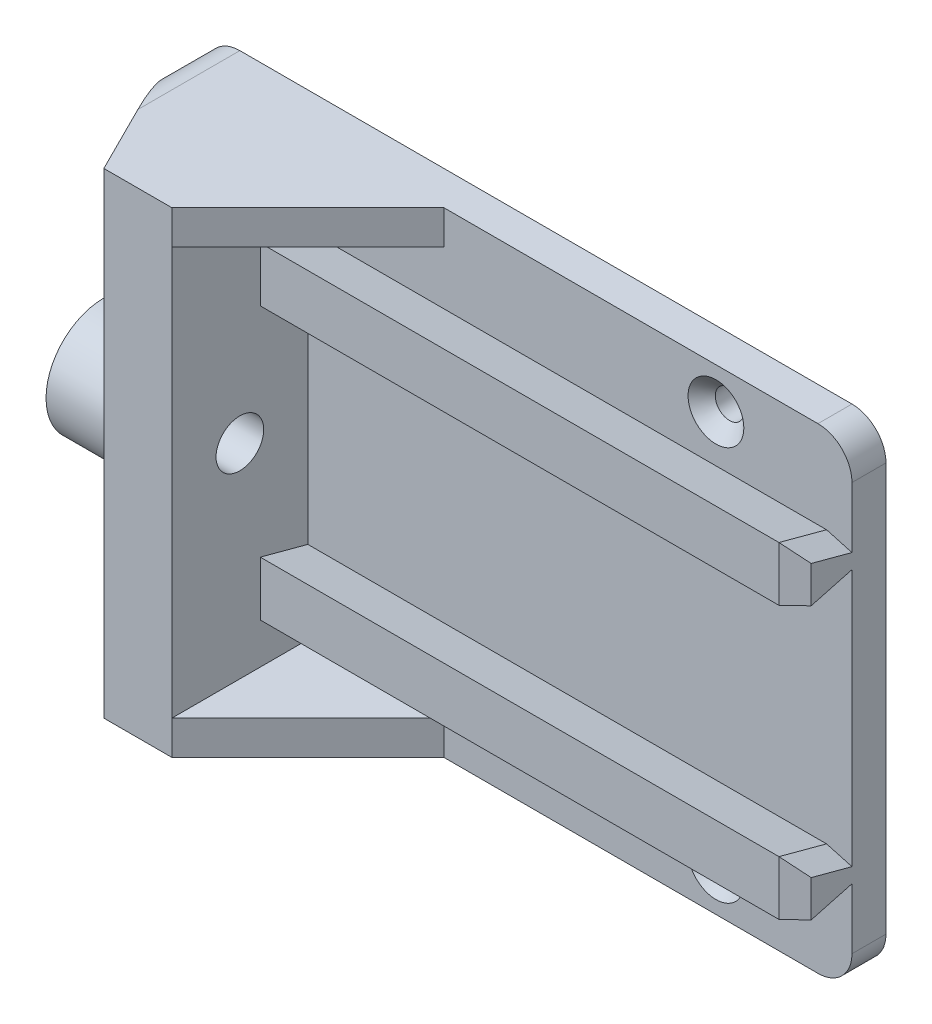
SolidWorks part; units mm, degrees
ref_plane "Piano frontale" through (0, 0, 0) normal (1, 0, 0) x (0, 1, 0)
ref_plane "Piano superiore - Base" through (0, 0, 0) normal (0, 0, 1) x (0, 1, 0)
ref_plane "Piano destro" through (0, 0, 0) normal (0, 1, 0) x (-1, 0, 0)
ref_plane "Alzata" through (0, 0, 30) normal (0, 0, 1) x (0, 1, 0)
ref_plane "Base scorrimento" through (0, 0, 5) normal (0, 0, 1) x (0, 1, 0)
sketch "Schizzo2" plane through (0, 0, 0) normal (0, 1, 0) x (-1, 0, 0)
  line L9 (-100, 0) -> (-100, 5)
  line L10 (38.5, 0) -> (-38.5, 0) construction
  line L11 (38.5, 5) -> (-38.5, 5) construction
  line L12 (-100, 5) -> (-20, 5)
  line L13 (-20, 5) -> (-20, 25)
  line L15 (-20, 25) -> (-10, 25)
  line L16 (-10, 25) -> (-10, 5)
  line L17 (-10, 5) -> (0, 5)
  line L18 (0, 5) -> (0, 0)
  line L19 (0, 0) -> (-100, 0)
  dimension "D1" = 10
  dimension "D2" = 80
  dimension "D3" = 10
  dimension "D4" = 20
extrude "Estrusione-Estrusione2" add sketch "Schizzo2" along normal mid plane 70
sketch "Schizzo8" plane through (20, 0, 0) normal (1, 0, 0) x (0, 1, 0)
  line L0 (-22.1244, 5) -> (-24, 12)
  line L1 (-24, 12) -> (-16, 12)
  line L2 (-16, 12) -> (-17.8756, 5)
  line L3 (-17.8756, 5) -> (-22.1244, 5)
  line L4 (35, 5) -> (-35, 5) construction
  line L5 (35, 5) -> (-35, 5) construction
  line L6 (0, -55) -> (0, 55) construction
  point P4 (-20, 5)
  dimension "D1" = 8
  dimension "D2" = 7
  dimension "D3" = 75
  dimension "D4" = 20
extrude "Estrusione-Estrusione4" add sketch "Schizzo8" along normal up to surface (80 mm away) up to face at (100, 0, 2.5)
sketch "Schizzo9" plane through (0, -35, 0) normal (0, -1, 0) x (1, 0, 0)
  line L0 (20, 25) -> (40, 5)
  line L1 (55, 5) -> (-55, 5) construction
  dimension "D1" = 45
rib "Nervatura2" sketch "Schizzo9" sketch "Schizzo9" thickness 5 extrusion direction parallel to sketch draft on no parameters "D1"=5
sketch "Schizzo10" plane through (0, -35, 0) normal (0, -1, 0) x (1, 0, 0)
  line L0 (10, 25) -> (0, 5)
rib "Nervatura3" sketch "Schizzo10" sketch "Schizzo10" thickness 5 extrusion direction parallel to sketch draft on no parameters "D1"=5
chamfer "Smusso2" distance 1 angle 75 3 edges at (100, -16.9378, 8.5) (100, -20, 12) (100, -23.0622, 8.5) first distance on face at (100, -10, 5.5)
mirror "Specchia3" about plane through (0, 0, 0) normal (0, 1, 0) of "Smusso2", "Estrusione-Estrusione4", "Nervatura2", "Nervatura3"
fillet "Raccordo2" radius 5 4 edges at (100, -35, 2.5) (0, -35, 2.5) (0, 35, 2.5) (100, 35, 2.5)
hole_wizard "Foro per Vite M6-1" positions "Schizzo11" profile "Schizzo12" hole size "M6" standard "Ansi Metric" end condition through all
sketch "Schizzo11" plane through (10, 0, 0) normal (-1, 0, 0) x (0, 0, 1)
  line L0 (55, 0) -> (-55, 0) construction
  line L1 (5, -55) -> (5, 55) construction
  point P1 (15, 0)
  dimension "D1" = 10
sketch "Schizzo12" plane through (10, 0, 15) normal (0, 1, 0) x (0, 0, 1)
  line L0 (0, 0) -> (0, 90)
  line L1 (0, 90) -> (3.5, 90)
  line L2 (3.5, 90) -> (3.5, 0)
  line L5 (3.5, 0) -> (0, 0)
  line L11 (0, -6.35) -> (0, 107.95) construction
  dimension "Thru Hole Dia." = 7
  dimension "Thru Hole Depth" = 90
hole_wizard "Foro svasato per Vite M3.5-1" positions "Schizzo13" profile "Schizzo14" countersink size "M3.5" standard "Ansi Metric" end condition through all
sketch "Schizzo13" plane through (0, 0, 5) normal (0, 0, 1) x (1, 0, 0)
  line L6 (40, -35) -> (95, -35) construction
  line L8 (95, -35) -> (5, -35) construction
  line L9 (0, 30) -> (0, -30) construction
  line L10 (100, -21.0891) -> (100, -30) construction
  point P0 (5, -20)
  point P2 (80, -29)
  dimension "D1" = 15
  dimension "D2" = 20
  dimension "D3" = 6
  dimension "D4" = 5
sketch "Schizzo14" plane through (5, -20, 5) normal (1, 0, 0) x (0, -1, 0)
  line L0 (0, 0) -> (0, 5)
  line L1 (0, 5) -> (2.1, 5)
  line L2 (2.1, 5) -> (2.1, 2)
  line L3 (2.1, 2) -> (4.1, 0)
  line L5 (4.1, 0) -> (0, 0)
  line L6 (-2.1, 2) -> (-4.1, 0) construction
  line L11 (0, -6.35) -> (0, 107.95) construction
  dimension "Thru Hole Dia." = 4.2
  dimension "Thru Hole Depth" = 5
  dimension "Near C'Sink Dia." = 8.2
  dimension "Near C'Sink Angle" = 90
mirror "Specchia4" about plane through (0, 0, 0) normal (0, 1, 0) of "Foro svasato per Vite M3.5-1"
sketch "Schizzo15" plane through (10, 0, 0) normal (-1, 0, 0) x (0, -1, 0)
  line L0 (-8.5, 15) -> (-8.5, 5)
  line L1 (55, 5) -> (-55, 5) construction
  line L2 (-8.5, 5) -> (8.5, 5)
  line L3 (8.5, 5) -> (8.5, 15)
  arc A0 (-8.5, 15) -> (8.5, 15) centre (0, 15) cw
  circle A1 centre (0, 15) radius 3.5 construction
  circle A2 centre (0, 15) radius 3.5
  point P10 (8.5, 5)
  point P11 (7.8859, 11.8277)
  point P12 (0, 0)
  dimension "D1" = 5
extrude "Estrusione-Estrusione5" add sketch "Schizzo15" along normal up to surface (10 mm away) up to face at (0, 0, 2.5)
